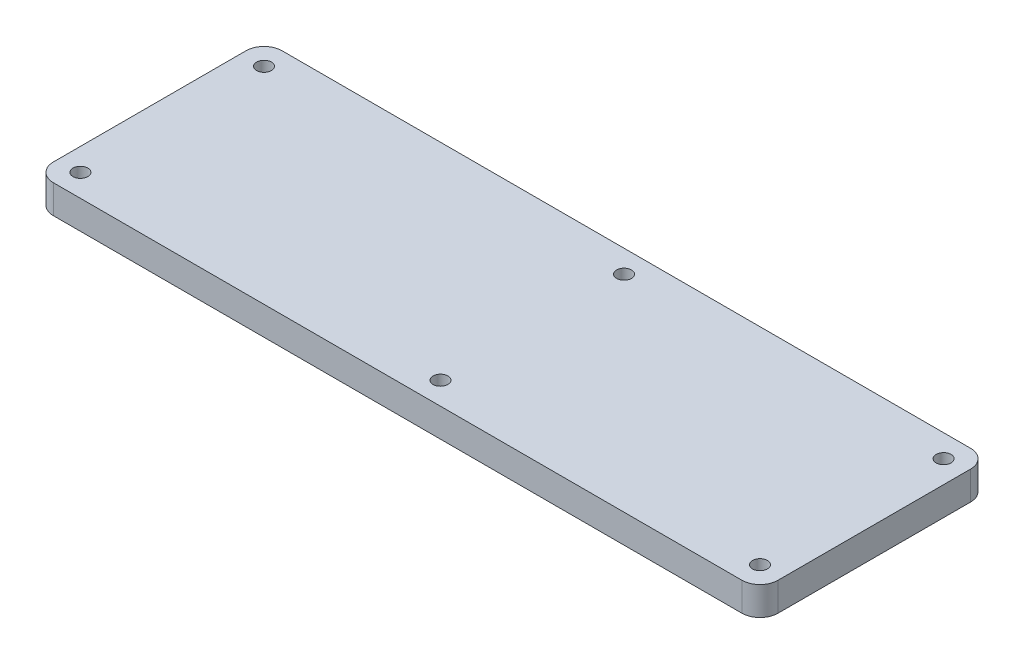
SolidWorks part; units mm, degrees
material "6061 Alloy"
ref_plane "Front Plane" through (0, 0, 0) normal (0, 0, 1) x (1, 0, 0)
ref_plane "Top Plane" through (0, 0, 0) normal (0, 1, 0) x (1, 0, 0)
ref_plane "Right Plane" through (0, 0, 0) normal (1, 0, 0) x (0, 0, -1)
sketch "Sketch1" plane through (0, 0, 0) normal (0, 1, 0) x (1, 0, 0)
  line L1 (-46.4116, -25.1858) -> (114.5884, -25.1858)
  line L2 (-46.4116, -25.1858) -> (-46.4116, 25.6142)
  line L3 (-46.4116, 25.6142) -> (114.5884, 25.6142)
  line L4 (114.5884, -25.1858) -> (114.5884, 25.6142)
  dimension "D1" = 50.8
  dimension "D2" = 161
extrude "Boss-Extrude1" add sketch "Sketch1" along normal blind 6.35
fillet "Fillet1" radius 4 4 edges at (114.5884, 3.175, 25.1858) (114.5884, 3.175, -25.6142) (-46.4116, 3.175, 25.1858) (-46.4116, 3.175, -25.6142)
hole_wizard "M4x0.7 Tapped Hole1" positions "Sketch3" profile "Sketch2" tap size "M4x0.7" standard "ANSI Metric" end condition through all
sketch "Sketch3" plane through (0, 6.35, 0) normal (0, 1, 0) x (1, 0, 0)
  line L0 (-42.4116, -25.1858) -> (110.5884, -25.1858) construction
  line L1 (-46.4116, 21.6142) -> (-46.4116, -21.1858) construction
  point P0 (-41.4116, -20.1858)
  point P2 (38.5884, -20.1858)
  point P4 (109.5884, -20.1858)
  point P6 (109.5884, 20.6142)
  point P8 (38.5884, 20.6142)
  point P10 (-41.4116, 20.6142)
  dimension "D1" = 5
  dimension "D2" = 5
  dimension "D3" = 85
  dimension "D4" = 156
  dimension "D5" = 45.8
sketch "Sketch2" plane through (-41.4116, 6.35, 20.1858) normal (1, 0, 0) x (0, 0, 1)
  line L0 (0, 0) -> (0, 6.35)
  line L1 (0, 6.35) -> (1.65, 6.35)
  line L2 (1.65, 6.35) -> (1.65, 0)
  line L5 (1.65, 0) -> (0, 0)
  line L11 (0, -6.35) -> (0, 107.95) construction
  dimension "Thru Tap Drill Dia." = 3.3
  dimension "Thru Tap Drill Depth" = 6.35
cosmetic thread "Hole Thread1" parameters "D2"=4
cosmetic thread "Hole Thread2" parameters "D2"=4
cosmetic thread "Hole Thread3" parameters "D2"=4
cosmetic thread "Hole Thread4" parameters "D2"=4
cosmetic thread "Hole Thread5" parameters "D2"=4
cosmetic thread "Hole Thread6" parameters "D2"=4
